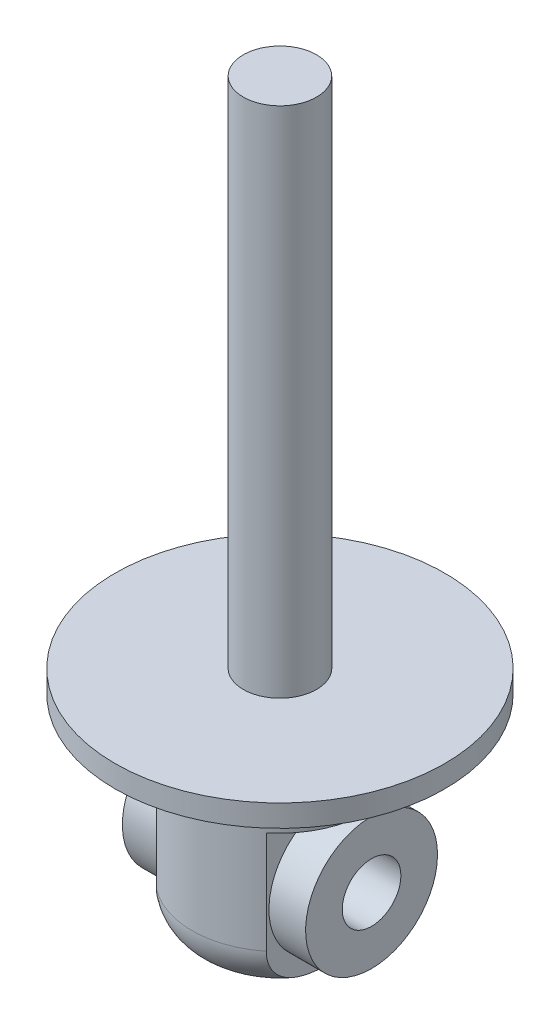
SolidWorks part; units mm, degrees
ref_plane "Front Plane" through (0, 0, 0) normal (0, 0, 1) x (1, 0, 0)
ref_plane "Top Plane" through (0, 0, 0) normal (0, 1, 0) x (1, 0, 0)
ref_plane "Right Plane" through (0, 0, 0) normal (1, 0, 0) x (0, 0, -1)
sketch "Sketch1" plane through (0, 0, 0) normal (0, 1, 0) x (1, 0, 0)
  circle A0 centre (0, 0) radius 22.5
  dimension "D1" = 45
extrude "Boss-Extrude1" add sketch "Sketch1" along normal blind 3
sketch "Sketch2" plane through (0, 3, 0) normal (0, 1, 0) x (1, 0, 0)
  circle A0 centre (0, 0) radius 5
  dimension "D1" = 10
extrude "Boss-Extrude2" add sketch "Sketch2" along normal blind 70
sketch "Sketch3" plane through (0, 0, 0) normal (0, -1, 0) x (1, 0, 0)
  circle A0 centre (0, 0) radius 12
  dimension "D1" = 24
extrude "Boss-Extrude3" add sketch "Sketch3" along normal blind 28
sketch "Sketch4" plane through (0, 0, 0) normal (0, 0, 1) x (1, 0, 0)
  line L0 (7.5, -28) -> (19.5268, -28)
  line L1 (-12, -28) -> (12, -28) construction
  line L2 (19.5268, -28) -> (19.5268, -8)
  line L3 (19.5268, -8) -> (7.5, -8)
  line L4 (7.5, -8) -> (7.5, -28)
  line L5 (0, 0) -> (0, -36.7614) construction
  line L6 (-19.5268, -8) -> (-7.5, -8)
  line L7 (-19.5268, -28) -> (-19.5268, -8)
  line L8 (-7.5, -28) -> (-19.5268, -28)
  line L9 (-7.5, -8) -> (-7.5, -28)
  dimension "D1" = 20
  dimension "D2" = 15
extrude "Cut-Extrude1" cut sketch "Sketch4" against normal through all both and the other way through all
sketch "Sketch5" plane through (7.5, 0, 0) normal (1, 0, 0) x (0, 0, -1)
  circle A0 centre (0, -17.2347) radius 4
  dimension "D1" = 8
fillet "Fillet1" radius 6 1 edges at (0, -28, 12)
sketch "Sketch6" plane through (7.5, 0, 0) normal (1, 0, 0) x (0, 0, -1)
  line L0 (0, 0) -> (0, -28) construction
  line L1 (-6, -28) -> (6, -28) construction
  circle A1 centre (0, -18) radius 4
  dimension "D1" = 10
  dimension "D2" = 8
extrude "Cut-Extrude3" cut sketch "Sketch6" against normal through all both
sketch "Sketch9" plane through (0, 0, 0) normal (1, 0, 0) x (0, 0, -1)
  circle A0 centre (0, -17.2347) radius 4
  circle A1 centre (0, -17.2347) radius 9
  dimension "D1" = 18
extrude "Boss-Extrude4" add sketch "Sketch9" along normal mid plane 25
